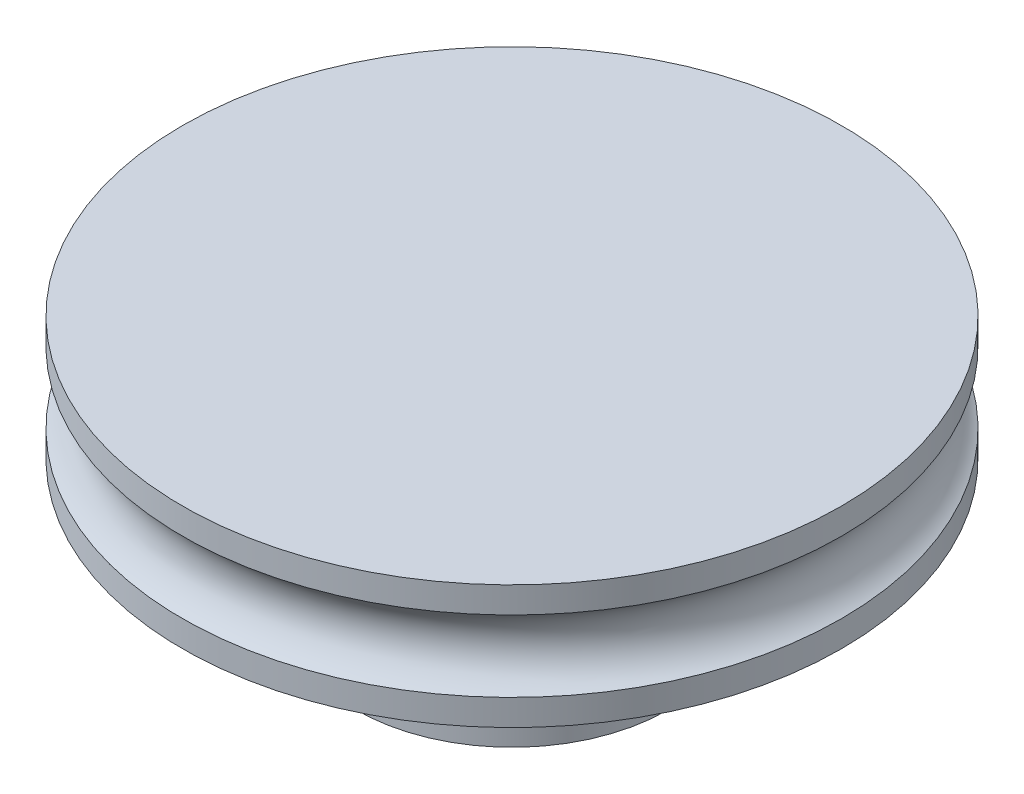
SolidWorks part; units mm, degrees
ref_plane "Front Plane" through (0, 0, 0) normal (0, 0, 1) x (1, 0, 0)
ref_plane "Top Plane" through (0, 0, 0) normal (0, 1, 0) x (1, 0, 0)
ref_plane "Right Plane" through (0, 0, 0) normal (1, 0, 0) x (0, 0, -1)
sketch "Sketch2" plane through (0, 0, 0) normal (0, 0, 1) x (1, 0, 0)
  line L1 (0, 0) -> (12.7, 0) construction
  line L10 (0, 0) -> (0, -2.3813)
  line L11 (0, -2.3813) -> (12.7, -2.3813)
  line L12 (12.7, -2.3813) -> (12.7, -1.3748)
  line L13 (0, 0) -> (0, 2.3813)
  line L14 (0, 2.3813) -> (12.7, 2.3813)
  line L15 (12.7, 2.3813) -> (12.7, 1.3748)
  arc A0 (12.7, -1.3748) -> (12.7, 1.3748) centre (13.4937, 0) cw
  point P8 (6, 1.0143)
  point P11 (6, 1.1887)
  point P12 (6, 1.955)
  dimension "D1" = 12.7
  dimension "D2" = 1.5875
  dimension "D3" = 0.7937
  dimension "D4" = 4.7625
revolve "Revolve1" add sketch "Sketch2" angle 360 about L13
sketch "Sketch7" plane through (0, -2.3812, 0) normal (0, -1, 0) x (-1, 0, 0)
  circle A0 centre (0, 0) radius 6.5
  dimension "D1" = 13
extrude "Boss-Extrude2" add sketch "Sketch7" along normal blind 0.3969
fillet "Fillet1" radius 0.7937 1 edges at (6.5, -2.3813, 0)
sketch "Sketch6" plane through (0, -2.7781, 0) normal (0, -1, 0) x (1, 0, 0)
  circle A0 centre (0, 0) radius 6
  point P3 (0.2102, -2.9121)
  point P5 (0, 0)
  dimension "D1" = 12
extrude "Boss-Extrude1" add sketch "Sketch6" along normal blind 5
sketch "Sketch5" plane through (0, -7.7781, 0) normal (0, -1, 0) x (1, 0, 0)
  line L0 (-1.7145, 0) -> (1.7145, 0) construction
  circle A0 centre (-1.7145, 0) radius 1.651
  circle A1 centre (1.7145, 0) radius 1.651
  point P4 (0, 0)
  dimension "D2" = 3.302
  dimension "D1" = 3.429
extrude "Cut-Extrude3" cut sketch "Sketch5" against normal blind 8.89
